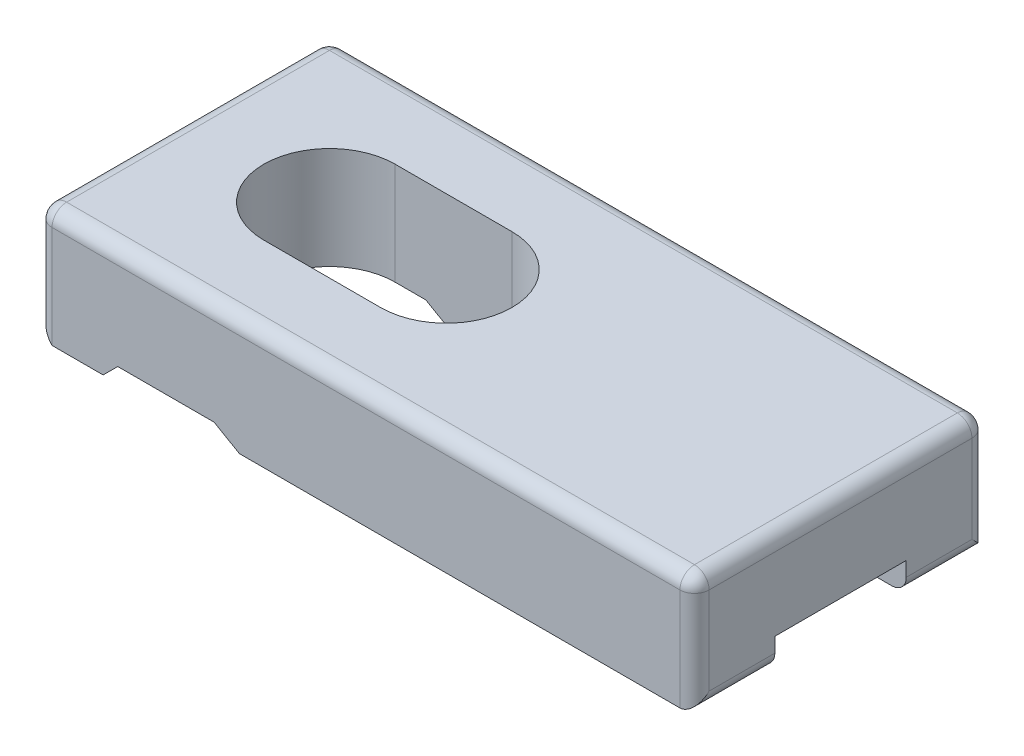
SolidWorks part; units mm, degrees
material "AISI 1045 钢，冷拔"
ref_plane "前视基准面" through (0, 0, 0) normal (0, 0, 1) x (1, 0, 0)
ref_plane "上视基准面" through (0, 0, 0) normal (0, 1, 0) x (1, 0, 0)
ref_plane "右视基准面" through (0, 0, 0) normal (1, 0, 0) x (0, 0, -1)
sketch "草图1" plane through (0, 0, 0) normal (0, 1, 0) x (1, 0, 0)
  line L0 (18, 10) -> (10, 10) construction
  line L1 (0, 0) -> (45, 0)
  line L2 (0, 0) -> (0, 20)
  line L3 (0, 20) -> (45, 20)
  line L4 (45, 0) -> (45, 20)
  line L5 (18, 5.5) -> (10, 5.5)
  line L6 (18, 14.5) -> (10, 14.5)
  arc A0 (18, 5.5) -> (18, 14.5) centre (18, 10) ccw
  arc A1 (10, 14.5) -> (10, 5.5) centre (10, 10) ccw
  point P7 (14, 10)
  dimension "D5" = 4.5
  dimension "D1" = 45
  dimension "D2" = 20
  dimension "D3" = 18
  dimension "D4" = 8
  dimension "D6" = 10
extrude "凸台-拉伸1" add sketch "草图1" along normal blind 8
sketch "草图2" plane through (0, 0, 0) normal (0, -1, 0) x (1, 0, 0)
  line L2 (45, 0) -> (45, -20) construction
  line L3 (45, -5.5) -> (45, -14.5)
  line L4 (45, -14.5) -> (10, -14.5)
  line L13 (10, -5.5) -> (45, -5.5)
  arc A0 (10, -5.5) -> (10, -14.5) centre (10, -10) ccw
extrude "切除-拉伸1" cut sketch "草图2" against normal blind 2
sketch "草图3" plane through (0, 0, 0) normal (0, -1, 0) x (1, 0, 0)
  line L0 (0, -5.5) -> (5.5, -5.5)
  line L1 (0, -20) -> (0, 0) construction
  line L3 (0, -14.5) -> (5.5, -14.5)
  line L4 (5.5, 0) -> (5.5, -5.5)
  line L5 (0, 0) -> (45, 0) construction
  line L6 (45, -20) -> (0, -20) construction
  line L7 (12.1, 0) -> (12.1, -20)
  line L8 (5.5, -14.5) -> (5.5, -20)
  line L9 (5.5, 0) -> (12.1, 0)
  line L10 (5.5, -20) -> (12.1, -20)
  line L11 (0, -5.5) -> (0, -14.5)
  dimension "D1" = 6.6
  dimension "D2" = 9
  dimension "D3" = 5.5
  dimension "D4" = 5.5
extrude "切除-拉伸2" cut sketch "草图3" against normal blind 1
chamfer "倒角1" distance 1 angle 45 4 edges at (0, 0, -17.25) (5.5, 0, -17.25) (5.5, 0, -2.75) (0, 0, -2.75)
chamfer "倒角2" distance 1 angle 60 2 edges at (12.1, 0, -17.25) (12.1, 0, -2.75) first distance on face at (12.1, 0.5, -17.25) first distance on face at (12.1, 0.5, -2.75)
fillet "圆角1" radius 1 10 edges at (22.5, 8, -20) (45, 8, -10) (22.5, 8, 0) (0, 8, -10) (45, 4, 0) (45, 4, -20) (0, 4.5, -20) (0, 4.5, 0) (45, 0, -17.25) (45, 0, -2.75)
